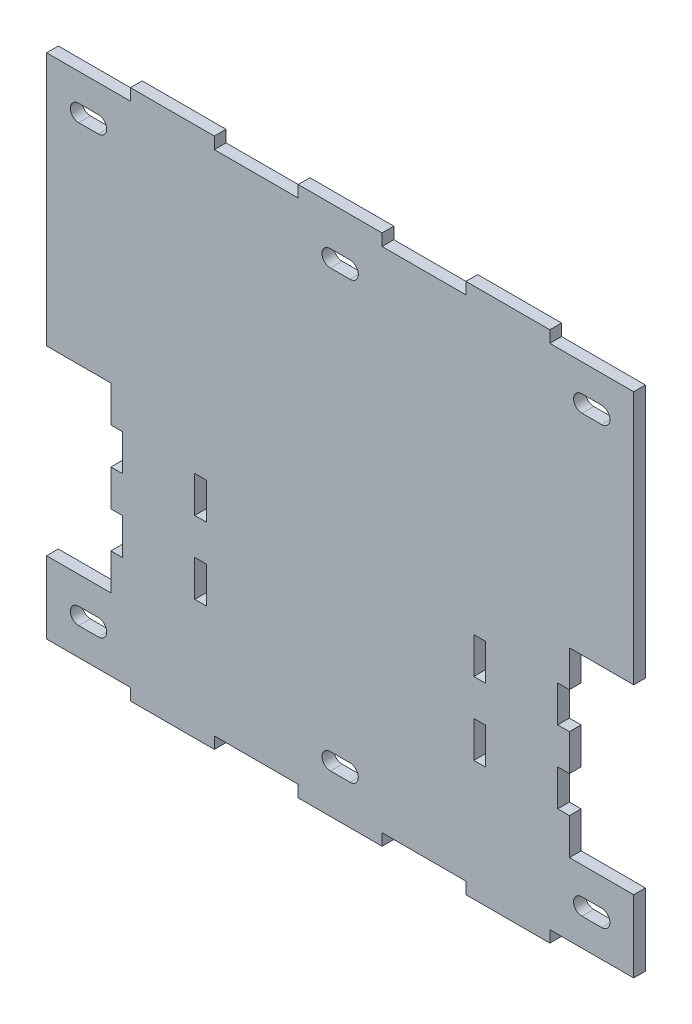
SolidWorks part; units mm, degrees
ref_plane "Front Plane" through (0, 0, 0) normal (0, 0, 1) x (1, 0, 0)
ref_plane "Top Plane" through (0, 0, 0) normal (0, 1, 0) x (1, 0, 0)
ref_plane "Right Plane" through (0, 0, 0) normal (1, 0, 0) x (0, 0, -1)
sketch "Sketch1" plane through (0, 0, 0) normal (0, 0, 1) x (1, 0, 0)
  line L1 (-133.35, 120.65) -> (133.35, 120.65)
  line L2 (-133.35, 120.65) -> (-133.35, -120.65)
  line L3 (-133.35, -120.65) -> (133.35, -120.65)
  line L4 (133.35, 120.65) -> (133.35, -120.65)
  line L5 (-133.35, 120.65) -> (133.35, -120.65) construction
  line L6 (-133.35, -120.65) -> (133.35, 120.65) construction
  point P0 (0, 0)
  dimension "D1" = 241.3
  dimension "D2" = 266.7
extrude "Boss-Extrude1" add sketch "Sketch1" along normal blind 5.334
sketch "Sketch2" plane through (0, 0, 0) normal (0, 0, -1) x (-1, 0, 0)
  line L0 (133.35, 120.65) -> (133.35, -120.65) construction
  line L1 (133.35, 0) -> (104.14, 0)
  line L2 (133.35, 0) -> (133.35, -82.55)
  line L3 (133.35, -82.55) -> (104.14, -82.55)
  line L4 (104.14, 0) -> (104.14, -82.55)
  line L5 (-133.35, -120.65) -> (-133.35, 120.65) construction
  line L6 (-133.35, 0) -> (-104.14, 0)
  line L7 (-133.35, 0) -> (-133.35, -82.55)
  line L8 (-133.35, -82.55) -> (-104.14, -82.55)
  line L9 (-104.14, 0) -> (-104.14, -82.55)
  line L10 (133.35, -120.65) -> (-133.35, -120.65) construction
  dimension "D1" = 82.55
  dimension "D2" = 82.55
  dimension "D3" = 38.1
  dimension "D4" = 38.1
  dimension "D5" = 29.21
  dimension "D6" = 29.21
extrude "Cut-Extrude1" cut sketch "Sketch2" against normal through all
sketch "Sketch9" plane through (0, 0, 5.334) normal (0, 0, 1) x (1, 0, 0)
  line L0 (-104.14, 0) -> (-104.14, -82.55) construction
  line L1 (-104.14, -16.51) -> (-98.806, -16.51)
  line L2 (-104.14, -16.51) -> (-104.14, -33.02)
  line L3 (-104.14, -33.02) -> (-98.806, -33.02)
  line L4 (-98.806, -16.51) -> (-98.806, -33.02)
  line L5 (-104.14, 0) -> (-98.806, 0) construction
  line L6 (-104.14, -49.53) -> (-98.806, -49.53)
  line L7 (-104.14, -49.53) -> (-104.14, -66.04)
  line L8 (-104.14, -66.04) -> (-98.806, -66.04)
  line L9 (-98.806, -49.53) -> (-98.806, -66.04)
  line L10 (-98.806, 0) -> (-98.806, -16.51) construction
  line L11 (-98.806, -33.02) -> (-98.806, -49.53) construction
  line L12 (-104.14, -82.55) -> (-98.806, -82.55) construction
  line L13 (-98.806, -82.55) -> (-98.806, -66.04) construction
  line L14 (0, -120.65) -> (0, 120.65) construction
  line L15 (-133.35, -120.65) -> (133.35, -120.65) construction
  line L16 (133.35, 120.65) -> (-133.35, 120.65) construction
  line L17 (98.806, -82.55) -> (98.806, -66.04) construction
  line L18 (104.14, -82.55) -> (98.806, -82.55) construction
  line L19 (98.806, -33.02) -> (98.806, -49.53) construction
  line L20 (98.806, 0) -> (98.806, -16.51) construction
  line L21 (104.14, 0) -> (98.806, 0) construction
  line L22 (98.806, -49.53) -> (98.806, -66.04)
  line L23 (104.14, -66.04) -> (98.806, -66.04)
  line L24 (104.14, -49.53) -> (104.14, -66.04)
  line L25 (104.14, -49.53) -> (98.806, -49.53)
  line L26 (98.806, -16.51) -> (98.806, -33.02)
  line L27 (104.14, -33.02) -> (98.806, -33.02)
  line L28 (104.14, -16.51) -> (104.14, -33.02)
  line L29 (104.14, -16.51) -> (98.806, -16.51)
  dimension "D1" = 5.334
extrude "Cut-Extrude2" cut sketch "Sketch9" against normal through all
sketch "Sketch23" plane through (0, 0, 5.334) normal (0, 0, 1) x (1, 0, 0)
  line L0 (-98.806, -24.765) -> (-61.976, -24.765) construction
  line L1 (-98.806, -33.02) -> (-98.806, -16.51) construction
  line L2 (-98.806, -16.51) -> (-60.706, -16.51) construction
  line L3 (-98.806, -33.02) -> (-60.706, -33.02) construction
  line L4 (-104.14, -41.275) -> (104.14, -41.275) construction
  line L5 (-104.14, -33.02) -> (-104.14, -49.53) construction
  line L6 (104.14, -49.53) -> (104.14, -33.02) construction
  line L7 (-98.806, -49.53) -> (-60.706, -49.53) construction
  line L8 (-98.806, -57.785) -> (-61.976, -57.785) construction
  line L9 (-98.806, -66.04) -> (-60.706, -66.04) construction
  line L10 (0, -120.65) -> (0, 120.65) construction
  line L11 (-133.35, -120.65) -> (133.35, -120.65) construction
  line L12 (133.35, 120.65) -> (-133.35, 120.65) construction
  line L13 (98.806, -66.04) -> (60.706, -66.04) construction
  line L14 (98.806, -49.53) -> (60.706, -49.53) construction
  line L15 (98.806, -33.02) -> (60.706, -33.02) construction
  line L16 (98.806, -16.51) -> (60.706, -16.51) construction
  line L17 (-60.706, -66.04) -> (-66.04, -66.04)
  line L18 (60.706, -16.51) -> (66.04, -16.51)
  line L19 (60.706, -16.51) -> (60.706, -33.02)
  line L20 (60.706, -33.02) -> (66.04, -33.02)
  line L21 (66.04, -16.51) -> (66.04, -33.02)
  line L22 (60.706, -49.53) -> (66.04, -49.53)
  line L23 (60.706, -49.53) -> (60.706, -66.04)
  line L24 (60.706, -66.04) -> (66.04, -66.04)
  line L25 (66.04, -49.53) -> (66.04, -66.04)
  line L26 (-66.04, -49.53) -> (-66.04, -66.04)
  line L27 (-60.706, -49.53) -> (-60.706, -66.04)
  line L28 (-60.706, -49.53) -> (-66.04, -49.53)
  line L29 (-60.706, -33.02) -> (-66.04, -33.02)
  line L30 (-66.04, -16.51) -> (-66.04, -33.02)
  line L31 (-60.706, -16.51) -> (-66.04, -16.51)
  line L32 (-60.706, -16.51) -> (-60.706, -33.02)
  line L33 (98.806, -16.51) -> (98.806, -33.02) construction
  dimension "D1" = 5.334
  dimension "D2" = 5.334
  dimension "D3" = 32.766
  dimension "D4" = 32.766
extrude "Cut-Extrude8" cut sketch "Sketch23" against normal through all
sketch "Sketch28" plane through (0, 0, 0) normal (0, 0, -1) x (-1, 0, 0)
  line L0 (133.35, -120.65) -> (-133.35, -120.65) construction
  line L1 (-133.35, -120.65) -> (-95.25, -120.65)
  line L2 (-133.35, -120.65) -> (-133.35, -115.316)
  line L3 (-133.35, -115.316) -> (-95.25, -115.316)
  line L4 (-95.25, -120.65) -> (-95.25, -115.316)
  line L5 (-57.15, -120.65) -> (-19.05, -120.65)
  line L6 (-57.15, -120.65) -> (-57.15, -115.316)
  line L7 (-57.15, -115.316) -> (-19.05, -115.316)
  line L8 (-19.05, -120.65) -> (-19.05, -115.316)
  line L9 (133.35, -82.55) -> (133.35, -120.65) construction
  line L10 (19.05, -120.65) -> (57.15, -120.65)
  line L11 (19.05, -120.65) -> (19.05, -115.316)
  line L12 (19.05, -115.316) -> (57.15, -115.316)
  line L13 (57.15, -120.65) -> (57.15, -115.316)
  line L14 (95.25, -120.65) -> (133.35, -120.65)
  line L16 (95.25, -115.316) -> (133.35, -115.316)
  line L17 (133.35, -120.65) -> (133.35, -115.316)
  line L18 (-95.25, -115.316) -> (-57.15, -115.316) construction
  line L19 (-19.05, -115.316) -> (19.05, -115.316) construction
  line L20 (95.25, -115.316) -> (57.15, -115.316) construction
  line L21 (133.35, 120.65) -> (133.35, -115.316) construction
  line L22 (133.35, -115.316) -> (133.5431, -115.1744) construction
  line L41 (95.25, -120.65) -> (95.25, -115.316)
  dimension "D1" = 5.334
extrude "Cut-Extrude13" cut sketch "Sketch28" against normal through all
sketch "Sketch29" plane through (0, 0, 0) normal (0, 0, -1) x (-1, 0, 0)
  line L0 (-133.35, 120.65) -> (133.35, 120.65) construction
  line L1 (-133.35, 120.65) -> (-95.25, 120.65)
  line L2 (-133.35, 120.65) -> (-133.35, 115.316)
  line L3 (-133.35, 115.316) -> (-95.25, 115.316)
  line L4 (-95.25, 120.65) -> (-95.25, 115.316)
  line L5 (-57.15, 120.65) -> (-19.05, 120.65)
  line L6 (-57.15, 120.65) -> (-57.15, 115.316)
  line L7 (-57.15, 115.316) -> (-19.05, 115.316)
  line L8 (-19.05, 120.65) -> (-19.05, 115.316)
  line L9 (133.35, 120.65) -> (133.35, 0) construction
  line L10 (19.05, 120.65) -> (57.15, 120.65)
  line L11 (19.05, 120.65) -> (19.05, 115.316)
  line L12 (19.05, 115.316) -> (57.15, 115.316)
  line L13 (57.15, 120.65) -> (57.15, 115.316)
  line L14 (95.25, 120.65) -> (133.35, 120.65)
  line L15 (95.25, 120.65) -> (95.25, 115.316)
  line L16 (95.25, 115.316) -> (133.35, 115.316)
  line L17 (133.35, 120.65) -> (133.35, 115.316)
  line L18 (-95.25, 115.316) -> (-57.15, 115.316) construction
  line L19 (19.05, 115.316) -> (-19.05, 115.316) construction
  line L20 (57.15, 115.316) -> (95.25, 115.316) construction
  dimension "D1" = 5.334
extrude "Cut-Extrude14" cut sketch "Sketch29" against normal through all
sketch "Sketch35" plane through (0, 0, 5.334) normal (0, 0, 1) x (1, 0, 0)
  line L0 (0, 120.65) -> (0, -120.65) construction
  line L1 (19.05, 120.65) -> (-19.05, 120.65) construction
  line L2 (-19.05, -120.65) -> (19.05, -120.65) construction
  line L3 (-133.35, -98.933) -> (133.35, -98.933) construction
  line L4 (-133.35, -82.55) -> (-133.35, -115.316) construction
  line L5 (133.35, -115.316) -> (133.35, -82.55) construction
  line L6 (-118.745, -82.55) -> (-118.745, -115.316) construction
  line L7 (-104.14, -82.55) -> (-133.35, -82.55) construction
  line L8 (-133.35, -115.316) -> (-95.25, -115.316) construction
  line L9 (-114.3, -115.316) -> (-114.3, -82.55) construction
  line L10 (118.745, -82.55) -> (118.745, -115.316) construction
  line L11 (133.35, -82.55) -> (104.14, -82.55) construction
  line L12 (95.25, -115.316) -> (133.35, -115.316) construction
  line L13 (114.3, -115.316) -> (114.3, -82.55) construction
  line L14 (-109.855, -98.933) -> (-118.745, -98.933) construction
  line L15 (-109.855, -102.743) -> (-118.745, -102.743)
  line L16 (-109.855, -95.123) -> (-118.745, -95.123)
  line L17 (109.855, -98.933) -> (118.745, -98.933) construction
  line L18 (109.855, -95.123) -> (118.745, -95.123)
  line L19 (109.855, -102.743) -> (118.745, -102.743)
  line L20 (0, 0) -> (43.5068, 0) construction
  line L21 (109.855, 98.933) -> (118.745, 98.933) construction
  line L22 (109.855, 95.123) -> (118.745, 95.123)
  line L23 (109.855, 102.743) -> (118.745, 102.743)
  line L24 (-109.855, 98.933) -> (-118.745, 98.933) construction
  line L25 (-109.855, 102.743) -> (-118.745, 102.743)
  line L26 (-109.855, 95.123) -> (-118.745, 95.123)
  line L27 (4.445, 98.933) -> (-4.445, 98.933) construction
  line L28 (4.445, 102.743) -> (-4.445, 102.743)
  line L29 (4.445, 95.123) -> (-4.445, 95.123)
  line L30 (4.445, -98.933) -> (-4.445, -98.933) construction
  line L31 (4.445, -102.743) -> (-4.445, -102.743)
  line L32 (4.445, -95.123) -> (-4.445, -95.123)
  arc A0 (-109.855, -102.743) -> (-109.855, -95.123) centre (-109.855, -98.933) ccw
  arc A1 (-118.745, -95.123) -> (-118.745, -102.743) centre (-118.745, -98.933) ccw
  arc A2 (109.855, -95.123) -> (109.855, -102.743) centre (109.855, -98.933) ccw
  arc A3 (118.745, -102.743) -> (118.745, -95.123) centre (118.745, -98.933) ccw
  arc A4 (109.855, 95.123) -> (109.855, 102.743) centre (109.855, 98.933) cw
  arc A5 (118.745, 102.743) -> (118.745, 95.123) centre (118.745, 98.933) cw
  arc A6 (-109.855, 102.743) -> (-109.855, 95.123) centre (-109.855, 98.933) cw
  arc A7 (-118.745, 95.123) -> (-118.745, 102.743) centre (-118.745, 98.933) cw
  arc A8 (4.445, 102.743) -> (4.445, 95.123) centre (4.445, 98.933) cw
  arc A9 (-4.445, 95.123) -> (-4.445, 102.743) centre (-4.445, 98.933) cw
  arc A10 (4.445, -102.743) -> (4.445, -95.123) centre (4.445, -98.933) ccw
  arc A11 (-4.445, -95.123) -> (-4.445, -102.743) centre (-4.445, -98.933) ccw
  point P30 (-114.3, -98.933)
  point P36 (114.3, -98.933)
  point P47 (114.3, 98.933)
  point P54 (-114.3, 98.933)
  point P63 (0, 98.933)
  point P70 (0, -98.933)
  dimension "D1" = 2
  dimension "D2" = 2
extrude "Cut-Extrude19" cut sketch "Sketch35" against normal through all
equation "\"MDF\"= .21in"
equation "\"Foamcore\"= .13in"
equation "\"Gmaterial\"= \"MDF\""
equation "\"D1@Sketch9\"=\"MDF\""
equation "\"D1@Sketch23\"=\"MDF\""
equation "\"D2@Sketch23\"=\"D1@Sketch23\""
equation "\"D1@Boss-Extrude1\"=\"MDF\""
equation "\"D3@Sketch23\"=1.29"
equation "\"D1@Sketch28\"=\"MDF\""
equation "\"D1@Sketch29\"=\"MDF\""
